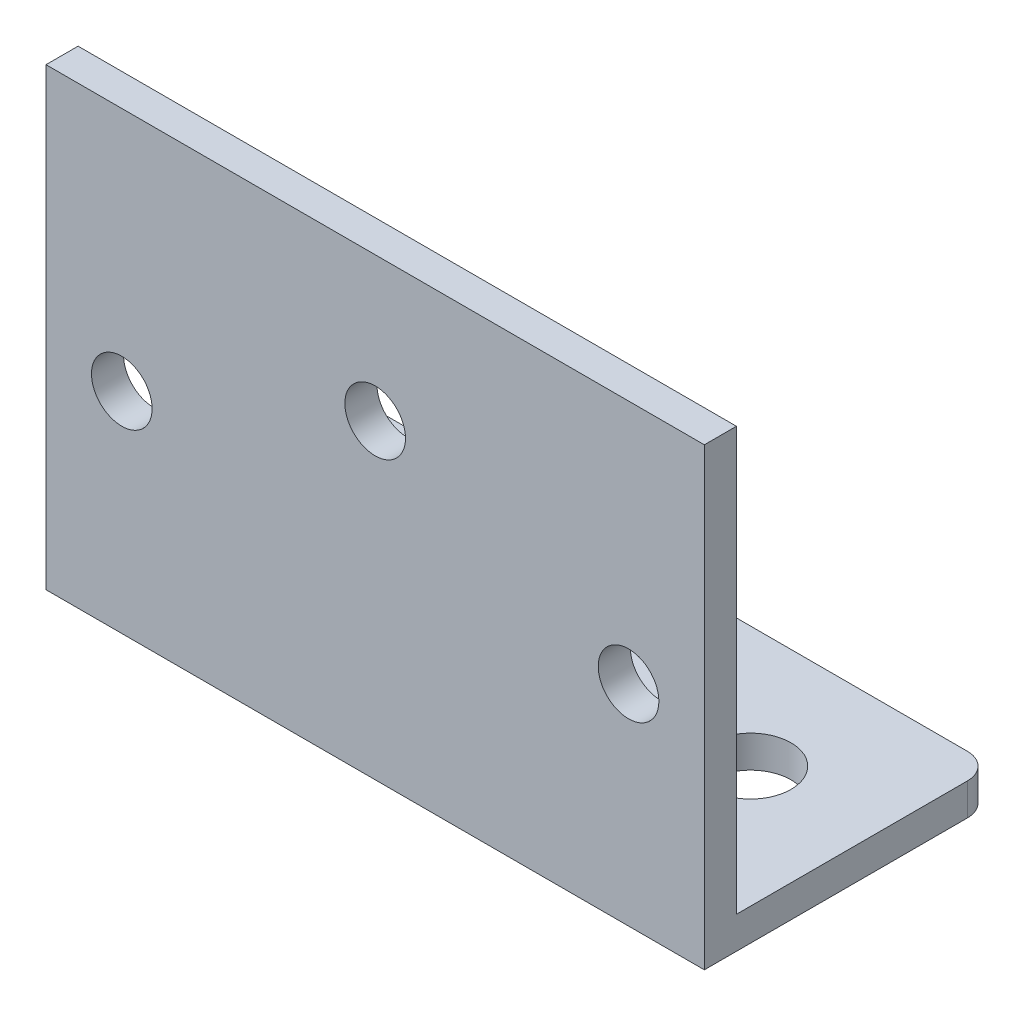
SolidWorks part; units mm, degrees
ref_plane "Front Plane" through (0, 0, 0) normal (0, 0, 1) x (1, 0, 0)
ref_plane "Top Plane" through (0, 0, 0) normal (0, 1, 0) x (1, 0, 0)
ref_plane "Right Plane" through (0, 0, 0) normal (1, 0, 0) x (0, 0, -1)
sketch "Sketch1" plane through (0, 0, 0) normal (0, 0, 1) x (1, 0, 0)
  line L5 (32.5247, -81.1853) -> (32.5247, -36.1853)
  line L6 (-99.1774, -81.1853) -> (98.5881, -81.1853) construction
  line L7 (-32.6263, -81.1853) -> (32.5247, -81.1853)
  line L8 (-32.6263, -36.1853) -> (-32.6263, -81.1853)
  line L9 (32.5247, -36.1853) -> (-32.6263, -36.1853) construction
  line L10 (-23.8633, -27.4223) -> (-47.4269, -27.4223)
  line L11 (-47.4269, -27.4223) -> (-47.4269, -55.4223)
  line L12 (-47.4269, -55.4223) -> (-79.3341, -55.4223)
  line L13 (-47.4269, -55.4223) -> (-47.4269, -70.4223)
  line L14 (-32.6263, -55.4223) -> (32.5247, -55.4223)
  line L15 (-32.6263, -70.4223) -> (32.5247, -70.4223)
  line L16 (-32.6263, -70.4223) -> (-25.1263, -70.4223)
  line L17 (-32.6263, -70.4223) -> (32.5247, -70.4223)
  line L18 (-32.6263, -70.4223) -> (-32.6263, -55.4223)
  line L19 (-32.6263, -55.4223) -> (32.5247, -55.4223)
  line L20 (32.5247, -70.4223) -> (32.5247, -55.4223)
  line L21 (-25.1263, -70.4223) -> (-25.1263, -60.4223)
  line L22 (-0.0508, -55.4223) -> (-0.0508, -70.4223)
  line L23 (32.5247, -36.1853) -> (-32.6263, -36.1853)
  line L24 (-32.6263, -36.1853) -> (-32.6263, -55.4223)
  line L25 (-32.6263, -55.4223) -> (32.5247, -55.4223)
  line L26 (32.5247, -55.4223) -> (32.5247, -36.1853)
  line L27 (32.5247, -55.4223) -> (-32.6263, -55.4223)
  line L28 (32.5247, -55.4223) -> (32.5247, -36.1853)
  line L29 (-32.6263, -55.4223) -> (-32.6263, -36.1853)
  line L30 (32.5247, -36.1853) -> (-32.6263, -36.1853)
  arc A0 (32.5247, -36.1853) -> (14.9987, -36.1853) centre (23.7617, -36.1853) ccw
  arc A1 (-15.1003, -36.1853) -> (14.9987, -36.1853) centre (-0.0508, -36.1853) ccw
  arc A2 (-15.1003, -36.1853) -> (-32.6263, -36.1853) centre (-23.8633, -36.1853) ccw
  circle A5 centre (-47.4269, -16.1853) radius 7.25
  circle A7 centre (-23.8633, -36.1853) radius 5.2324
  circle A8 centre (23.7617, -36.1853) radius 5.2324
  circle A9 centre (-25.1263, -60.4223) radius 3
  circle A10 centre (25.0247, -60.4223) radius 3
  circle A11 centre (-0.0508, -50.4223) radius 3
  dimension "D2" = 10.4648
  dimension "D4" = 8.763
  dimension "D5" = 10
  dimension "D1" = 45
  dimension "D3" = 47.625
  dimension "D6" = 10
  dimension "D7" = 15
extrude "Boss-Extrude1" add sketch "Sketch1" along normal blind 3.175 contours L15 L8 L7 L5 L17 | L19 L22 L17 L5 A10 | A9 L15 L22 L14 L8 | A11 A1 L23 A7 L8 L14 L19 L5 A8 | A11 A1 L30 | L30 A8 | L30 A7 region at (-0.0508, -75.8038, 0) region at (15.6972, -63.0758, 0) region at (16.237, -54.743, 0) region at (-15.7988, -63.0758, 0) region at (23.7617, -38.406, 0) region at (-0.0508, -42.1932, 0) region at (-23.8633, -38.406, 0)
sketch "Sketch2" plane through (0, 0, 0) normal (0, 0, -1) x (-1, 0, 0)
  line L0 (32.6263, -81.1853) -> (-32.5247, -81.1853) construction
  line L1 (32.6263, -81.1853) -> (-32.5247, -81.1853)
  line L3 (-32.5247, -81.1853) -> (32.6263, -81.1853)
  line L4 (-32.5247, -81.1853) -> (-32.5247, -78.0103)
  line L5 (-32.5247, -78.0103) -> (32.6263, -78.0103)
  line L6 (32.6263, -81.1853) -> (32.6263, -78.0103)
  line L7 (32.6263, -14.5103) -> (32.6263, -81.1853) construction
  dimension "D1" = 3.175
  dimension "D2" = 65.151
extrude "Boss-Extrude2" add sketch "Sketch2" along normal blind 25.4 contours L4 L5 L6 L3
fillet "Fillet1" radius 2.54 2 edges at (-32.6263, -79.5978, -25.4) (32.5247, -79.5978, -25.4)
sketch "Sketch3" plane through (0, -78.0103, 0) normal (0, 1, 0) x (1, 0, 0)
  line L0 (-20.6263, 25.4) -> (-20.6263, 13.4)
  line L4 (29.9847, 25.4) -> (-30.0863, 25.4) construction
  line L8 (20.5247, 25.4) -> (20.5247, 13.4)
  line L9 (-20.6263, 13.4) -> (-32.6263, 13.4)
  line L10 (-32.6263, 22.86) -> (-32.6263, 0) construction
  line L11 (20.5247, 13.4) -> (32.5247, 13.4)
  line L12 (32.5247, 22.86) -> (32.5247, 0) construction
  circle A1 centre (19.7054, 15.0943) radius 4 construction
  circle A12 centre (20.5247, 13.4) radius 4
  circle A13 centre (-20.6263, 13.4) radius 4
  point P8 (19.7054, 15.0943)
  point P16 (-20.6263, 13.4)
  dimension "D1" = 12
  dimension "D3" = 8
  dimension "D4" = 8
  dimension "D2" = 12
  dimension "D5" = 12
  dimension "D6" = 12
extrude "Cut-Extrude1" cut sketch "Sketch3" against normal up to surface (3.175 mm away) contours A13 | A12 up to face at (-0.0508, -81.1853, -15.2037)
